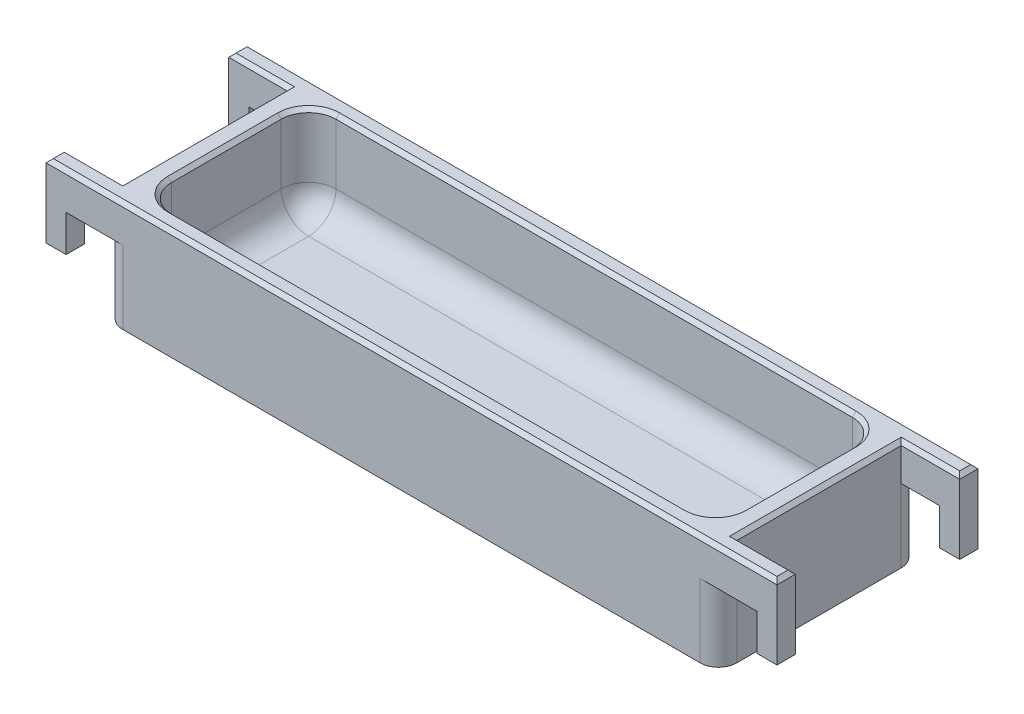
SolidWorks part; units mm, degrees
ref_plane "Front Plane" through (0, 0, 0) normal (0, 0, 1) x (1, 0, 0)
ref_plane "Top Plane" through (0, 0, 0) normal (0, 1, 0) x (1, 0, 0)
ref_plane "Right Plane" through (0, 0, 0) normal (1, 0, 0) x (0, 0, -1)
sketch "Sketch1" plane through (0, 0, 0) normal (0, 1, 0) x (1, 0, 0)
  line L0 (-84, -15) -> (-84, -20)
  line L1 (-100, 30) -> (100, 30)
  line L2 (-100, 30) -> (-100, 25)
  line L3 (-100, -20) -> (-84, -20)
  line L4 (100, 30) -> (100, 25)
  line L5 (-78.1495, -20) -> (78.1495, -20)
  line L6 (-100, -20) -> (-84, -20)
  line L8 (-84, 25) -> (-84, -15)
  line L10 (84, 25) -> (84, -15)
  line L13 (-84, 25) -> (-100, 25)
  line L14 (-84, 25) -> (-84, -15)
  line L18 (84, -15) -> (84, 25)
  line L19 (84, 25) -> (100, 25)
  line L21 (-100, -20) -> (-84, -20)
  line L24 (-78.1495, -15) -> (-78.1495, 25)
  line L25 (-78.1495, 25) -> (78.1495, 25)
  line L26 (78.1495, -15) -> (78.1495, 25)
  line L27 (84, -20) -> (100, -20)
  line L28 (84, -20) -> (100, -20)
  line L29 (-78.1495, 25) -> (78.1495, 25)
  line L30 (-100, -20) -> (-100, -25)
  line L31 (-100, -25) -> (100, -25)
  line L32 (100, -20) -> (100, -25)
  line L33 (-78.1495, -15) -> (-78.1495, -20)
  line L34 (78.1495, -15) -> (78.1495, -20)
  line L36 (84, -20) -> (84, -15)
  line L37 (-78.1495, -20) -> (78.1495, -20)
  point P0 (0, 0)
  point P6 (0, 0)
  point P15 (0, 0)
  dimension "D1" = 200
  dimension "D2" = 50
  dimension "D3" = 5
  dimension "D4" = 168
extrude "Boss-Extrude1" add sketch "Sketch1" along normal blind 30 contours L10 L19 L4 L1 L2 L13 L8 L3 L26 L24 L25 region at (-81.9258, 0, -5)
sketch "Sketch3" plane through (0, 0, -25) normal (0, 0, 1) x (1, 0, 0)
  line L1 (-84, 0) -> (-94.5, 0)
  line L2 (-84, 0) -> (-84, 20)
  line L3 (-84, 20) -> (-94.5, 20)
  line L4 (-94.5, 11.6805) -> (-94.5, 20)
  line L7 (-100, 0) -> (-94.5, 0)
  line L9 (-100, 30) -> (-100, 0) construction
  line L10 (-100, 10) -> (-94.5, 10)
  line L11 (-94.5, 10) -> (-94.5, 11.6805)
  line L12 (-100, 10) -> (-100, 0)
  dimension "D1" = 10.5
  dimension "D2" = 20
extrude "Cut-Extrude1" cut sketch "Sketch3" against normal blind 5
ref_plane "Plane1" through (0, 0, -2.5) normal (0, 0, 1) x (1, 0, 0)
mirror "Mirror1" about plane through (0, 0, -2.5) normal (0, 0, 1) of "Cut-Extrude1" second plane through (0, 0, 0) second plane normal (1, 0, 0)
sketch "Sketch4" plane through (0, 0, 0) normal (0, -1, 0) x (1, 0, 0)
  line L10 (-78.1495, 20) -> (78.1495, 20)
  line L11 (-78.1495, 20) -> (-78.1495, -25)
  line L12 (-78.1495, -25) -> (78.1495, -25)
  line L13 (78.1495, 20) -> (78.1495, -25)
extrude "Boss-Extrude2" add sketch "Sketch4" against normal blind 5
fillet "Fillet1" radius 7.5 8 edges at (0, 5, -25) (78.1495, 5, -2.5) (-78.1495, 5, -2.5) (78.1495, 17.5, -25) (-78.1495, 17.5, -25) (0, 5, 20) (-78.1495, 17.5, 20) (78.1495, 17.5, 20)
fillet "Fillet2" radius 5 4 edges at (84, 10, -30) (-84, 10, -30) (84, 10, 25) (-84, 10, 25)
chamfer "Chamfer1" distance 1 angle 45 20 edges at (100, 30, 22.5) (0, 30, 25) (-100, 30, 22.5) (-92, 30, 20) (-84, 30, -2.5) (-92, 30, -25) (-100, 30, -27.5) (0, 30, -30) (100, 30, -27.5) (92, 30, -25) (84, 30, -2.5) (92, 30, 20) (75.9528, 30, -22.8033) (0, 30, -25) (-75.9528, 30, -22.8033) (-78.1495, 30, -2.5) (-75.9528, 30, 17.8033) (0, 30, 20) (75.9528, 30, 17.8033) (78.1495, 30, -2.5)
sketch "Sketch5" plane through (0, 5, 0) normal (0, 1, 0) x (1, 0, 0)
  text T0 "<b>Jasmine</b>" font "Century Gothic" height in points 72
extrude "Cut-Extrude2" [suppressed] cut sketch "Sketch5" against normal blind 1
chamfer "Chamfer8" [suppressed] distance 1 angle 45
